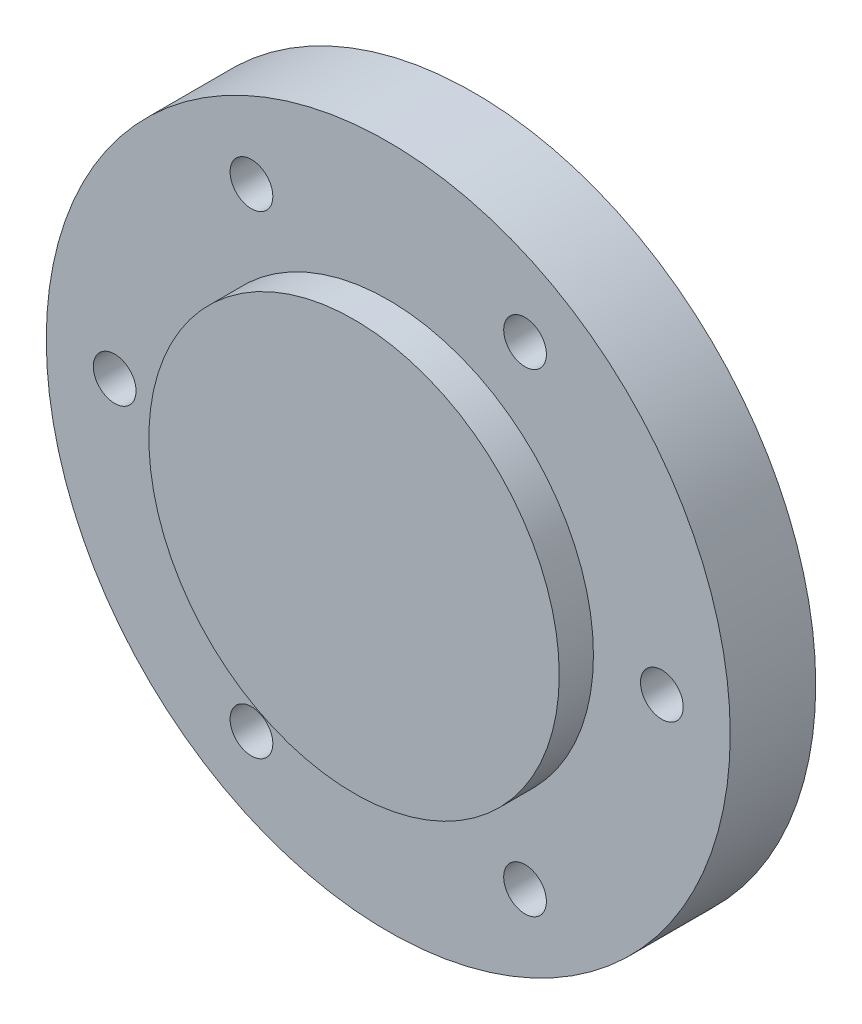
SolidWorks part; units mm, degrees
ref_plane "Front Plane" through (0, 0, 0) normal (0, 0, 1) x (1, 0, 0)
ref_plane "Top Plane" through (0, 0, 0) normal (0, 1, 0) x (1, 0, 0)
ref_plane "Right Plane" through (0, 0, 0) normal (1, 0, 0) x (0, 0, -1)
sketch "SK_Disc" plane through (0, 0, 0) normal (0, 0, 1) x (1, 0, 0)
  circle A0 centre (0, 0) radius 20
  dimension "D_disc" = 40
extrude "Output_Disc" add sketch "SK_Disc" along normal blind 5
ref_plane "PL_Mount" through (0, 0, 5) normal (0, 0, 1) x (1, 0, 0)
sketch "SK_Pilot" plane through (0, 0, 5) normal (0, 0, 1) x (1, 0, 0)
  circle A0 centre (0, 0) radius 12
  dimension "D_pil" = 24
extrude "Pilot_Boss" add sketch "SK_Pilot" along normal blind 2
sketch "SK_OutHole" plane through (0, 0, 5) normal (0, 0, 1) x (1, 0, 0)
  circle A0 centre (16, 0) radius 1.25
  dimension "D_oh" = 2.5
  dimension "R_oh" = 16
extrude "Output_Tapped_Hole" cut sketch "SK_OutHole" against normal blind 5
ref_axis "AX_Joint" through (0, 0, -0.35) along (0, 0, 1)
pattern_circular "Output_Hole_Pattern" count 6 over 360 about axis through (0, 0, -0.35) along (0, 0, 1) of "Output_Tapped_Hole"
equation "\"D_out\" = 40"
equation "\"T_out\" = 5"
equation "\"PCD_out\" = 32"
equation "\"D_pilot\" = 24"
equation "\"H_pilot\" = 2"
equation "\"D_out_hole\" = 2.5"
equation "\"D_disc@SK_Disc\" = \"D_out\""
equation "\"D1@Output_Disc\" = \"T_out\""
equation "\"D_pil@SK_Pilot\" = \"D_pilot\""
equation "\"D1@Pilot_Boss\" = \"H_pilot\""
equation "\"D_oh@SK_OutHole\" = \"D_out_hole\""
equation "\"R_oh@SK_OutHole\" = \"PCD_out\"/2"
